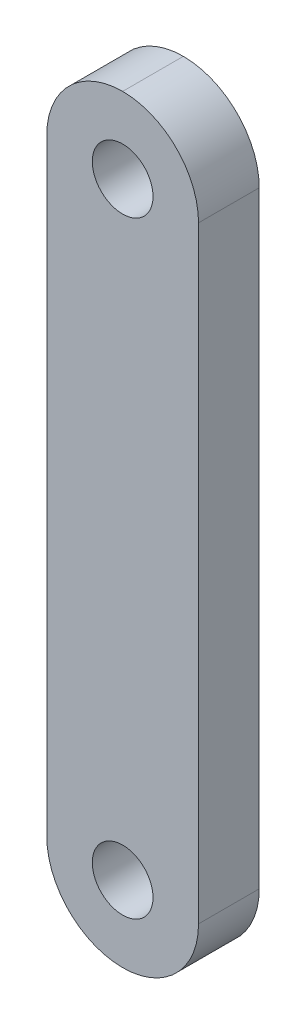
SolidWorks part; units mm, degrees
ref_plane "Plan de face" through (0, 0, 0) normal (0, 0, 1) x (1, 0, 0)
ref_plane "Plan de dessus" through (0, 0, 0) normal (0, 1, 0) x (1, 0, 0)
ref_plane "Plan de droite" through (0, 0, 0) normal (1, 0, 0) x (0, 0, -1)
sketch "Esquisse1" plane through (0, 0, 0) normal (0, 0, 1) x (1, 0, 0)
  line L0 (-25, 125) -> (25, -125) construction
  line L1 (-25, -125) -> (25, -125)
  line L2 (-25, -125) -> (-25, 125)
  line L3 (-25, 125) -> (25, 125)
  line L4 (25, -125) -> (25, 125)
  point P4 (0, 0)
  dimension "D1" = 50
  dimension "D2" = 250
extrude "Boss.-Extru.1" add sketch "Esquisse1" along normal blind 20
sketch "Esquisse2" plane through (0, 0, 20) normal (0, 0, 1) x (1, 0, 0)
  line L0 (-25, -125) -> (25, -125) construction
  line L1 (25, 125) -> (-25, 125) construction
  circle A0 centre (0, -100) radius 10
  circle A1 centre (0, 100) radius 10
  dimension "D1" = 20
  dimension "D3" = 20
  dimension "D2" = 25
  dimension "D4" = 25
extrude "Enlèv. mat.-Extru.1" cut sketch "Esquisse2" against normal up to next
fillet "Congé1" radius 25 4 edges at (-25, -125, 10) (25, -125, 10) (-25, 125, 10) (25, 125, 10)
